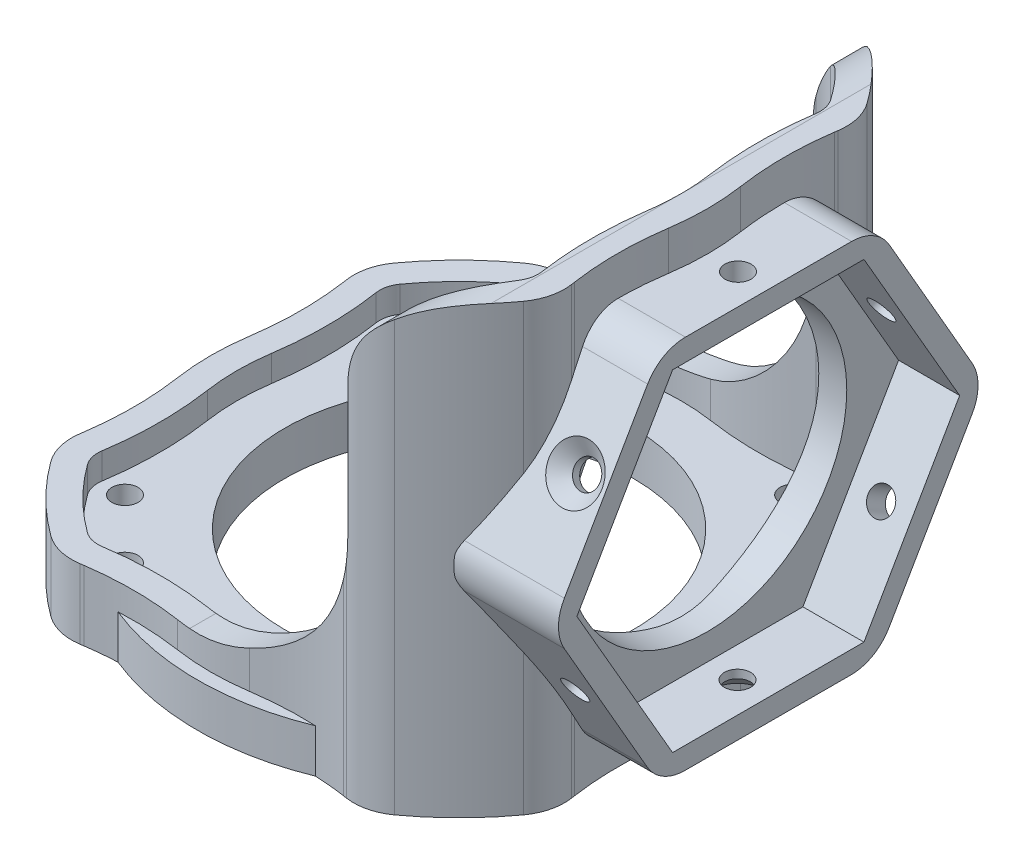
SolidWorks part; units mm, degrees
ref_plane "前视基准面" through (0, 0, 0) normal (0, 0, 1) x (1, 0, 0)
ref_plane "上视基准面" through (0, 0, 0) normal (0, 1, 0) x (1, 0, 0)
ref_plane "右视基准面" through (0, 0, 0) normal (1, 0, 0) x (0, 0, -1)
sketch "草图1" plane through (0, 0, 0) normal (0, 1, 0) x (1, 0, 0)
  line L0 (0, 0) -> (0, 46.6195) construction
  line L1 (0, 0) -> (-41.7463, 0) construction
  line L2 (-22.5267, 15.7734) -> (0, 0) construction
  line L3 (-15.7734, 22.5267) -> (0, 0) construction
  circle A0 centre (0, 0) radius 30
  circle A1 centre (0, 0) radius 20
  circle A2 centre (0, 0) radius 27.5 construction
  circle A3 centre (-22.5267, 15.7734) radius 1.5
  circle A4 centre (-15.7734, 22.5267) radius 1.5
  circle A5 centre (22.5267, 15.7734) radius 1.5
  circle A6 centre (15.7734, 22.5267) radius 1.5
  circle A7 centre (22.5267, -15.7734) radius 1.5
  circle A8 centre (15.7734, -22.5267) radius 1.5
  circle A9 centre (-22.5267, -15.7734) radius 1.5
  circle A10 centre (-15.7734, -22.5267) radius 1.5
  dimension "D1" = 60
  dimension "D2" = 40
  dimension "D3" = 55
  dimension "D5" = 3
  dimension "D4" = 35
  dimension "D6" = 35
extrude "凸台-拉伸1" add sketch "草图1" along normal blind 5
sketch "草图2" plane through (0, 5, 0) normal (0, 1, 0) x (1, 0, 0)
  line L0 (0, 0) -> (39.9587, 0) construction
  line L1 (0, 0) -> (0, -36.8515) construction
  line L2 (0, 0) -> (21.5668, 21.5668) construction
  arc A0 (24.7368, -3.2548) -> (24.949, 0.2177) centre (0, 0) ccw construction
  arc A1 (25.1774, -3.6784) -> (25.1774, 3.6784) centre (0.5, 0) ccw
  arc A2 (24.949, 0.2177) -> (24.6762, 3.686) centre (0, 0) ccw construction
  arc A3 (25.1774, 3.6784) -> (24.7671, 8.11) centre (64.7402, 9.5757) cw
  arc A4 (24.2388, 9.2464) -> (24.6762, 3.686) centre (64.2373, 9.5955) ccw construction
  arc A5 (24.7671, 8.11) -> (25.2125, 15.7044) centre (64.7402, 9.5757) cw
  arc A6 (24.7179, 15.7777) -> (24.2388, 9.2464) centre (64.2373, 9.5955) ccw construction
  arc A7 (25.2125, 15.7044) -> (24.675, 17.9275) centre (22.248, 16.1641) ccw
  arc A8 (24.7179, 15.7777) -> (24.2705, 17.6336) centre (22.248, 16.1641) ccw construction
  arc A9 (24.675, 17.9275) -> (17.9275, 24.675) centre (0, 0) ccw
  circle A10 centre (0, 0) radius 30 construction
  arc A11 (28.1446, 4.1207) -> (28.1446, -4.1207) centre (0.5, 0) cw
  arc A12 (28.1446, 4.1207) -> (28.1241, 14.8917) centre (64.7402, 9.5757) cw
  arc A13 (28.1241, 14.8917) -> (28.1806, 15.2677) centre (65.7457, 9.4297) cw
  arc A14 (28.1806, 15.2677) -> (27.1021, 19.6908) centre (22.248, 16.1641) ccw
  arc A15 (19.6908, 27.1021) -> (27.1021, 19.6908) centre (0, 0) cw
  arc A16 (15.2677, 28.1806) -> (19.6908, 27.1021) centre (16.1641, 22.248) cw
  arc A17 (14.8917, 28.1241) -> (15.2677, 28.1806) centre (9.4297, 65.7457) ccw
  arc A18 (4.1207, 28.1446) -> (14.8917, 28.1241) centre (9.5757, 64.7402) ccw
  arc A19 (4.1207, 28.1446) -> (-4.1207, 28.1446) centre (0, 0.5) ccw
  arc A20 (15.7044, 25.2125) -> (17.9275, 24.675) centre (16.1641, 22.248) cw
  arc A21 (8.11, 24.7671) -> (15.7044, 25.2125) centre (9.5757, 64.7402) ccw
  arc A22 (3.6784, 25.1774) -> (8.11, 24.7671) centre (9.5757, 64.7402) ccw
  arc A23 (-3.6784, 25.1774) -> (3.6784, 25.1774) centre (0, 0.5) cw
  arc A24 (-3.6784, 25.1774) -> (-8.11, 24.7671) centre (-9.5757, 64.7402) cw
  arc A25 (-8.11, 24.7671) -> (-15.7044, 25.2125) centre (-9.5757, 64.7402) cw
  arc A26 (-15.7044, 25.2125) -> (-17.9275, 24.675) centre (-16.1641, 22.248) ccw
  arc A27 (-4.1207, 28.1446) -> (-14.8917, 28.1241) centre (-9.5757, 64.7402) cw
  arc A28 (-14.8917, 28.1241) -> (-15.2677, 28.1806) centre (-9.4297, 65.7457) cw
  arc A29 (-15.2677, 28.1806) -> (-19.6908, 27.1021) centre (-16.1641, 22.248) ccw
  arc A30 (-19.6908, 27.1021) -> (-27.1021, 19.6908) centre (0, 0) ccw
  arc A31 (-28.1806, 15.2677) -> (-27.1021, 19.6908) centre (-22.248, 16.1641) cw
  arc A32 (-28.1241, 14.8917) -> (-28.1806, 15.2677) centre (-65.7457, 9.4297) ccw
  arc A33 (-28.1446, 4.1207) -> (-28.1241, 14.8917) centre (-64.7402, 9.5757) ccw
  arc A34 (-28.1446, 4.1207) -> (-28.1446, -4.1207) centre (-0.5, 0) ccw
  arc A35 (-24.675, 17.9275) -> (-17.9275, 24.675) centre (0, 0) cw
  arc A36 (-25.2125, 15.7044) -> (-24.675, 17.9275) centre (-22.248, 16.1641) cw
  arc A37 (-24.7671, 8.11) -> (-25.2125, 15.7044) centre (-64.7402, 9.5757) ccw
  arc A38 (-25.1774, 3.6784) -> (-24.7671, 8.11) centre (-64.7402, 9.5757) ccw
  arc A39 (-25.1774, -3.6784) -> (-25.1774, 3.6784) centre (-0.5, 0) cw
  arc A40 (-25.1774, -3.6784) -> (-24.7671, -8.11) centre (-64.7402, -9.5757) cw
  arc A41 (-24.7671, -8.11) -> (-25.2125, -15.7044) centre (-64.7402, -9.5757) cw
  arc A42 (-25.2125, -15.7044) -> (-24.675, -17.9275) centre (-22.248, -16.1641) ccw
  arc A43 (-24.675, -17.9275) -> (-17.9275, -24.675) centre (0, 0) ccw
  arc A44 (-28.1446, -4.1207) -> (-28.1241, -14.8917) centre (-64.7402, -9.5757) cw
  arc A45 (-28.1241, -14.8917) -> (-28.1806, -15.2677) centre (-65.7457, -9.4297) cw
  arc A46 (-28.1806, -15.2677) -> (-27.1021, -19.6908) centre (-22.248, -16.1641) ccw
  arc A47 (-19.6908, -27.1021) -> (-27.1021, -19.6908) centre (0, 0) cw
  arc A48 (-15.2677, -28.1806) -> (-19.6908, -27.1021) centre (-16.1641, -22.248) cw
  arc A49 (-14.8917, -28.1241) -> (-15.2677, -28.1806) centre (-9.4297, -65.7457) ccw
  arc A50 (-4.1207, -28.1446) -> (-14.8917, -28.1241) centre (-9.5757, -64.7402) ccw
  arc A51 (-15.7044, -25.2125) -> (-17.9275, -24.675) centre (-16.1641, -22.248) cw
  arc A52 (-8.11, -24.7671) -> (-15.7044, -25.2125) centre (-9.5757, -64.7402) ccw
  arc A53 (-3.6784, -25.1774) -> (-8.11, -24.7671) centre (-9.5757, -64.7402) ccw
  arc A54 (-3.6784, -25.1774) -> (3.6784, -25.1774) centre (0, -0.5) ccw
  arc A55 (3.6784, -25.1774) -> (8.11, -24.7671) centre (9.5757, -64.7402) cw
  arc A56 (8.11, -24.7671) -> (15.7044, -25.2125) centre (9.5757, -64.7402) cw
  arc A57 (15.7044, -25.2125) -> (17.9275, -24.675) centre (16.1641, -22.248) ccw
  arc A58 (4.1207, -28.1446) -> (-4.1207, -28.1446) centre (0, -0.5) cw
  arc A59 (4.1207, -28.1446) -> (14.8917, -28.1241) centre (9.5757, -64.7402) cw
  arc A60 (14.8917, -28.1241) -> (15.2677, -28.1806) centre (9.4297, -65.7457) cw
  arc A61 (15.2677, -28.1806) -> (19.6908, -27.1021) centre (16.1641, -22.248) ccw
  arc A62 (19.6908, -27.1021) -> (27.1021, -19.6908) centre (0, 0) ccw
  arc A63 (28.1806, -15.2677) -> (27.1021, -19.6908) centre (22.248, -16.1641) cw
  arc A64 (28.1241, -14.8917) -> (28.1806, -15.2677) centre (65.7457, -9.4297) ccw
  arc A65 (28.1446, -4.1207) -> (28.1241, -14.8917) centre (64.7402, -9.5757) ccw
  arc A66 (24.675, -17.9275) -> (17.9275, -24.675) centre (0, 0) cw
  arc A67 (25.2125, -15.7044) -> (24.675, -17.9275) centre (22.248, -16.1641) cw
  arc A68 (24.7671, -8.11) -> (25.2125, -15.7044) centre (64.7402, -9.5757) ccw
  arc A69 (25.1774, -3.6784) -> (24.7671, -8.11) centre (64.7402, -9.5757) ccw
  point P7 (24.95, 0)
  point P9 (25.45, 0)
  point P13 (0, -24.95)
  point P60 (0, 25.45)
  point P61 (0, 24.95)
  point P85 (-25.45, 0)
  point P86 (-24.95, 0)
  point P129 (0, -25.45)
  dimension "D2" = 30.5
  dimension "D1" = 0.5
extrude "凸台-拉伸2" add sketch "草图2" along normal blind 46 and the other way blind 5
sketch "草图3" plane through (0, 0, 0) normal (0, 0, 1) x (1, 0, 0)
  line L0 (-30.7273, 8) -> (-30.7273, -1.7514)
  line L2 (-30.7273, -1.7514) -> (-34.3096, -1.7514)
  line L3 (-34.3096, -1.7514) -> (-34.3096, 55.8818)
  line L4 (-34.3096, 55.8818) -> (36.2257, 55.8818)
  line L5 (36.2257, 55.8818) -> (36.2257, -1.7514)
  line L6 (36.2257, -1.7514) -> (28.45, -1.7514)
  line L7 (28.45, -1.7514) -> (28.45, 51)
  line L8 (28.45, 5) -> (28.45, 51) construction
  line L9 (28.45, 51) -> (25.45, 51)
  line L10 (14.8917, 51) -> (4.1207, 51) construction
  line L11 (15.45, 41) -> (15.45, 26)
  line L12 (-2.55, 8) -> (-30.7273, 8)
  line L13 (-27.7815, 5) -> (-30, 5) construction
  arc A0 (15.45, 26) -> (-2.55, 8) centre (-2.55, 26) cw
  arc A1 (25.45, 51) -> (15.45, 41) centre (25.45, 41) ccw
  point P20 (15.45, 51)
  dimension "D1" = 18
  dimension "D2" = 10
  dimension "D3" = 3
  dimension "D4" = 3
extrude "切除-拉伸1" cut sketch "草图3" along normal through all and the other way through all
sketch "草图4" plane through (28.45, 0, 0) normal (1, 0, 0) x (0, 0, -1)
  line L0 (0, 0) -> (0, 56.7093) construction
  line L1 (28.1446, 5) -> (27.7402, 5) construction
  circle A2 centre (0, 25) radius 20 construction
  circle A3 centre (0, 25) radius 16
  dimension "D1" = 40
  dimension "D2" = 32
extrude "切除-拉伸2" cut sketch "草图4" against normal blind 22 and the other way blind 19
sketch "草图5" plane through (28.45, 0, 0) normal (1, 0, 0) x (0, 0, -1)
  line L1 (13.8308, 5.9813) -> (23.3793, 22.4685)
  line L2 (23.386, 27.4685) -> (13.882, 43.9813)
  line L3 (9.5553, 46.4871) -> (-9.4973, 46.5128)
  line L4 (-13.8308, 44.0187) -> (-23.3793, 27.5315)
  line L5 (-23.386, 22.5315) -> (-13.882, 6.0187)
  line L6 (-9.5553, 3.5129) -> (9.4973, 3.4872)
  circle A0 centre (0, 25) radius 16
  arc A1 (-4.1207, 40.4603) -> (-14.8917, 30.8513) centre (0, 25) ccw construction
  circle A2 centre (0, 25) radius 22.5 construction
  circle A3 centre (0, 25) radius 21.5 construction
  arc A4 (13.882, 43.9813) -> (9.5553, 46.4871) centre (9.5485, 41.4871) ccw
  arc A5 (23.3793, 22.4685) -> (23.386, 27.4685) centre (19.0525, 24.9743) ccw
  arc A6 (13.8308, 5.9813) -> (9.4973, 3.4872) centre (9.504, 8.4872) cw
  arc A7 (-13.882, 6.0187) -> (-9.5553, 3.5129) centre (-9.5485, 8.5129) ccw
  arc A8 (-23.3793, 27.5315) -> (-23.386, 22.5315) centre (-19.0525, 25.0257) ccw
  arc A9 (-9.4973, 46.5128) -> (-13.8308, 44.0187) centre (-9.504, 41.5128) ccw
  dimension "D1" = 45
  dimension "D2" = 43
  dimension "D3" = 5
sketch "草图7" plane through (0, 51, 0) normal (0, 1, 0) x (1, 0, 0)
  line L0 (28.1241, -14.8917) -> (31.1027, -14.0835)
  line L1 (31.1027, -14.0835) -> (31.1027, 14.2516)
  line L2 (31.1027, 14.2516) -> (28.1241, 14.8917)
  arc A0 (28.1241, -14.8917) -> (28.1446, -4.1207) centre (64.7402, -9.5757) cw
  arc A1 (28.1446, -4.1207) -> (28.1241, -14.8917) centre (64.7402, -9.5757) ccw construction
  arc A2 (28.1446, -4.1207) -> (28.1446, 4.1207) centre (0.5, 0) ccw
  arc A3 (28.1446, 4.1207) -> (28.1241, 14.8917) centre (64.7402, 9.5757) cw
extrude "切除-拉伸3" cut sketch "草图7" against normal through all
extrude "凸台-拉伸4" add sketch "草图5" along normal blind 7 and the other way blind 5
sketch "草图8" plane through (0, 51, 0) normal (0, 1, 0) x (1, 0, 0)
  line L0 (17.9275, -24.675) -> (17.9275, 24.675)
  arc A0 (17.9275, -24.675) -> (24.675, -17.9275) centre (0, 0) ccw
  arc A1 (24.675, -17.9275) -> (25.2125, -15.7044) centre (22.248, -16.1641) ccw
  arc A2 (25.2125, -15.7044) -> (25.1774, -3.6784) centre (64.7402, -9.5757) cw
  arc A3 (25.1774, -3.6784) -> (25.45, 0) centre (0.5, 0) ccw
  arc A4 (25.45, 0) -> (25.1774, 3.6784) centre (0.5, 0) ccw
  arc A5 (25.1774, 3.6784) -> (25.2125, 15.7044) centre (64.7403, 9.5757) cw
  arc A6 (25.2125, 15.7044) -> (24.675, 17.9275) centre (22.248, 16.1641) ccw
  arc A7 (24.675, 17.9275) -> (17.9275, 24.675) centre (0, 0) ccw
extrude "切除-拉伸4" cut sketch "草图8" against normal up to surface (46 mm away) up to face at (0, 5, 28.5061)
sketch "草图9" plane through (35.45, 0, 0) normal (1, 0, 0) x (0, 0, -1)
  line L1 (10.9697, 6) -> (21.9393, 25)
  line L2 (21.9393, 25) -> (10.9697, 44)
  line L3 (10.9697, 44) -> (-10.9697, 44)
  line L4 (-10.9697, 44) -> (-21.9393, 25)
  line L5 (-21.9393, 25) -> (-10.9697, 6)
  line L6 (-10.9697, 6) -> (10.9697, 6)
  circle A2 centre (0, 25) radius 19 construction
  dimension "D2" = 38
extrude "切除-拉伸5" cut sketch "草图9" against normal blind 7
sketch "草图10" plane through (0, 17.0543, 29.4472) normal (0, 0.5012, 0.8654) x (1, 0, 0)
  line L0 (35.45, 21.6338) -> (31.95, 21.6338) construction
  line L1 (35.45, 31.16) -> (35.45, 12.1075) construction
  circle A0 centre (31.95, 21.6338) radius 1.5
  circle A1 centre (31.95, 21.6338) radius 3 construction
  dimension "D2" = 3
  dimension "D3" = 6
  dimension "D1" = 3.5
sketch "草图11" plane through (0, -4.5041, 7.8256) normal (0, -0.4988, 0.8667) x (1, 0, 0)
  line L0 (35.45, 21.6675) -> (31.95, 21.6675) construction
  line L1 (35.45, 31.1937) -> (35.45, 12.1412) construction
  circle A0 centre (31.95, 21.6675) radius 1.5
  circle A1 centre (31.95, 21.6675) radius 3 construction
  dimension "D1" = 6
  dimension "D2" = 3
  dimension "D3" = 3.5
extrude "切除-拉伸6" cut sketch "草图10" against normal through all
extrude "切除-拉伸7" cut sketch "草图11" against normal through all
sketch "草图12" plane through (0, 3.5, -0.0047) normal (0, -1, 0.0013) x (1, 0, 0)
  line L0 (35.45, 0.0337) -> (31.95, 0.0337) construction
  line L1 (35.45, 9.56) -> (35.45, -9.4926) construction
  circle A0 centre (31.95, 0.0337) radius 1.5
  circle A1 centre (31.95, 0.0337) radius 3 construction
  dimension "D2" = 3
  dimension "D3" = 6
  dimension "D1" = 3.5
extrude "切除-拉伸8" cut sketch "草图12" against normal through all
sketch "草图13" plane through (0, 0, 0) normal (0, -1, 0) x (1, 0, 0)
  line L0 (-14.0904, 25.6743) -> (-15.604, 24.7943)
  line L1 (-15.604, 24.7943) -> (-17.3639, 24.0199)
  line L2 (-17.3639, 24.0199) -> (-20.8838, 20.4649)
  line L3 (-20.8838, 20.4649) -> (-23.9813, 16.8394)
  line L4 (-23.9813, 16.8394) -> (-26.0197, 14.4535)
  line L5 (-26.0197, 14.4535) -> (-25.5653, 18.6521)
  line L6 (-25.5653, 18.6521) -> (-20.8838, 24.1315)
  line L7 (-20.8838, 24.1315) -> (-17.2837, 26.2246)
  line L8 (-17.2837, 26.2246) -> (-14.0904, 25.6743)
  line L9 (-21.4676, -19.5744) -> (-18.6381, -22.3759)
  line L10 (-18.6381, -22.3759) -> (-16.3467, -24.3337)
  line L11 (-16.3467, -24.3337) -> (-15.3102, -25.612)
  line L12 (-15.3102, -25.612) -> (-16.3467, -26.4523)
  line L13 (-16.3467, -26.4523) -> (-20.653, -24.0308)
  line L14 (-20.653, -24.0308) -> (-24.3427, -20.1015)
  line L15 (-24.3427, -20.1015) -> (-25.7925, -17.6078)
  line L16 (-25.7925, -17.6078) -> (-26.0197, -15.2619)
  line L17 (-26.0197, -15.2619) -> (-25.0137, -15.4353)
  line L18 (-25.0137, -15.4353) -> (-23.3178, -17.8374)
  line L19 (-23.3178, -17.8374) -> (-21.4676, -19.5744)
  line L20 (23.7623, -17.4526) -> (24.8079, -16.1747)
  line L21 (24.8079, -16.1747) -> (25.9115, -15.6326)
  line L22 (25.9115, -15.6326) -> (26.2407, -17.1234)
  line L23 (26.2407, -17.1234) -> (25.0402, -19.4275)
  line L24 (25.0402, -19.4275) -> (22.5619, -22.0027)
  line L25 (22.5619, -22.0027) -> (19.2897, -24.4617)
  line L26 (19.2897, -24.4617) -> (16.7339, -25.9913)
  line L27 (16.7339, -25.9913) -> (14.7396, -25.7589)
  line L28 (14.7396, -25.7589) -> (15.3397, -24.6072)
  line L29 (15.3397, -24.6072) -> (16.9544, -24.0987)
  line L30 (16.9544, -24.0987) -> (18.775, -22.207)
  line L31 (18.775, -22.207) -> (22.5619, -18.9047)
  line L32 (22.5619, -18.9047) -> (23.7623, -17.4526)
  line L33 (14.9976, 25.5005) -> (16.9544, 24.4377)
  line L34 (16.9544, 24.4377) -> (19.002, 22.7487)
  line L35 (19.002, 22.7487) -> (20.71, 20.718)
  line L36 (20.71, 20.718) -> (22.5619, 19.01)
  line L37 (22.5619, 19.01) -> (24.0501, 16.8394)
  line L38 (24.0501, 16.8394) -> (25.8018, 15.2238)
  line L39 (25.8018, 15.2238) -> (26.0618, 16.5239)
  line L40 (26.0618, 16.5239) -> (24.2428, 19.2523)
  line L41 (24.2428, 19.2523) -> (22.3922, 21.4524)
  line L42 (22.3922, 21.4524) -> (19.856, 23.7916)
  line L43 (19.856, 23.7916) -> (17.8147, 25.6743)
  line L44 (17.8147, 25.6743) -> (15.976, 26.2246)
  line L45 (15.976, 26.2246) -> (14.9976, 25.5005)
extrude "凸台-拉伸5" add sketch "草图13" against normal up to surface (5 mm away) up to face at (0, 5, 28.5061)
chamfer "倒角1" distance 1.55 angle 45 11 edges at (31.95, 37.0249, -17.8858) (31.95, 34.4771, 19.3568) (31.95, 3.498, -1.471) (22.5267, 0, -17.2734) (15.7734, 0, -24.0267) (22.5267, 0, 17.2734) (15.7734, 0, 24.0267) (-15.7734, 0, 21.0267) (-22.5267, 0, 14.2734) (-15.7734, 0, -21.0267) (-22.5267, 0, -14.2734)
